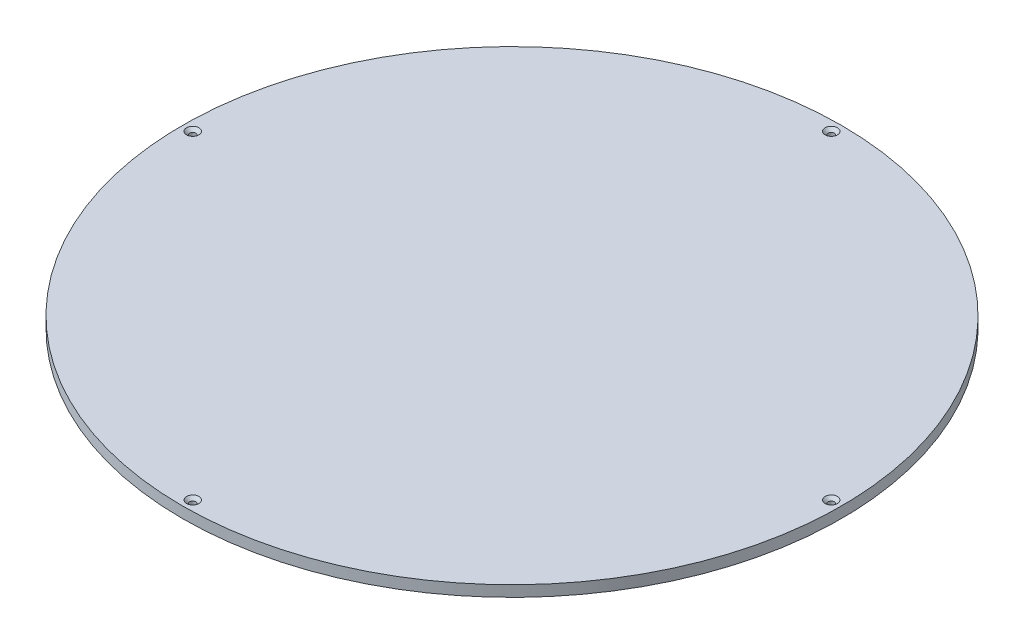
SolidWorks part; units mm, degrees
material "Pine"
ref_plane "Front Plane" through (0, 0, 0) normal (0, 0, 1) x (1, 0, 0)
ref_plane "Top Plane" through (0, 0, 0) normal (0, 1, 0) x (1, 0, 0)
ref_plane "Right Plane" through (0, 0, 0) normal (1, 0, 0) x (0, 0, -1)
sketch "Sketch1" plane through (0, 0, 0) normal (0, 1, 0) x (1, 0, 0)
  line L0 (-8.7941, 0) -> (197.1788, 0) construction
  circle A0 centre (0, 0) radius 160
  circle A1 centre (155, 0) radius 1.5
  circle A2 centre (0, -155) radius 1.5
  circle A3 centre (-155, 0) radius 1.5
  circle A4 centre (0, 155) radius 1.5
  point P16 (0, 0)
  dimension "D1" = 320
  dimension "D2" = 3
  dimension "D3" = 155
  dimension "D4" = 4
extrude "Boss-Extrude1" add sketch "Sketch1" against normal blind 5.333
chamfer "Chamfer1" distance 1.5 angle 45 4 edges at (155, 0, 1.5) (-155, 0, 1.5) (0, 0, -153.5) (0, 0, 156.5)
equation "\"rod_diameter\"= 8"
equation "\"rod_hole_thickness\"= 4"
equation "\"rod_radius\"= \"rod_diameter\" / 2"
equation "\"platter_diameter\"= 320"
equation "\"platter_radius\"= \"platter_diameter\" / 2"
equation "\"extruder_mount_hole_spacing\"= 75"
equation "\"arm_rod_spacing\"= 40"
equation "\"motor_level_rod_spacing\"= 15"
equation "\"linear_bearing_diameter\"= 15"
equation "\"z_rod_spacing\"= 75"
equation "\"platter_rod_spacing\"= 50"
equation "\"rod_nut_thickness\"= 6.5"
equation "\"rod_nut_inscribed_diameter\"= 13"
equation "\"z_height\"= 350"
equation "\"D1@Sketch1\"=\"platter_diameter\""
equation "\"D3@Sketch1\"=\"platter_radius\"-5"
equation "\"top_frame_spacing\"= 90"
equation "\"z_drive_rod_offset\"= 12"
equation "\"gear_pitch\"=2"
equation "\"r_gear_teeth\"= 450"
equation "\"theta_gear_teeth\"= 385"
equation "\"sheet_thickness\"=5.333"
equation "\"sheet_tab_hole_thickness\"= \"sheet_thickness\""
equation "\"sheet_tab_width\"= \"sheet_thickness\"*2"
equation "\"sheet_double_tab_width\"= 35"
equation "\"sheet_bolt_diameter\"= 3"
equation "\"sheet_bolt_length\"= 16"
equation "\"sheet_nut_diameter\"= 5.5"
equation "\"sheet_nut_thickness\"= 2.5"
equation "\"sheet_nut_depth\"= 10"
equation "\"bearing_outside_diameter\"= 22"
equation "\"bearing_thickness\"= 7"
equation "\"corner_part_thickness\"= \"sheet_thickness\" + \"bearing_thickness\""
equation "\"setscrew_nut_diameter\"= 6"
equation "\"setscrew_nut_thickness\"= 3"
equation "\"setscrew_bolt_diameter\"= 3"
equation "\"motor_shaft_diameter\"= 5.7"
equation "\"D1@Boss-Extrude1\"= \"sheet_thickness\""
